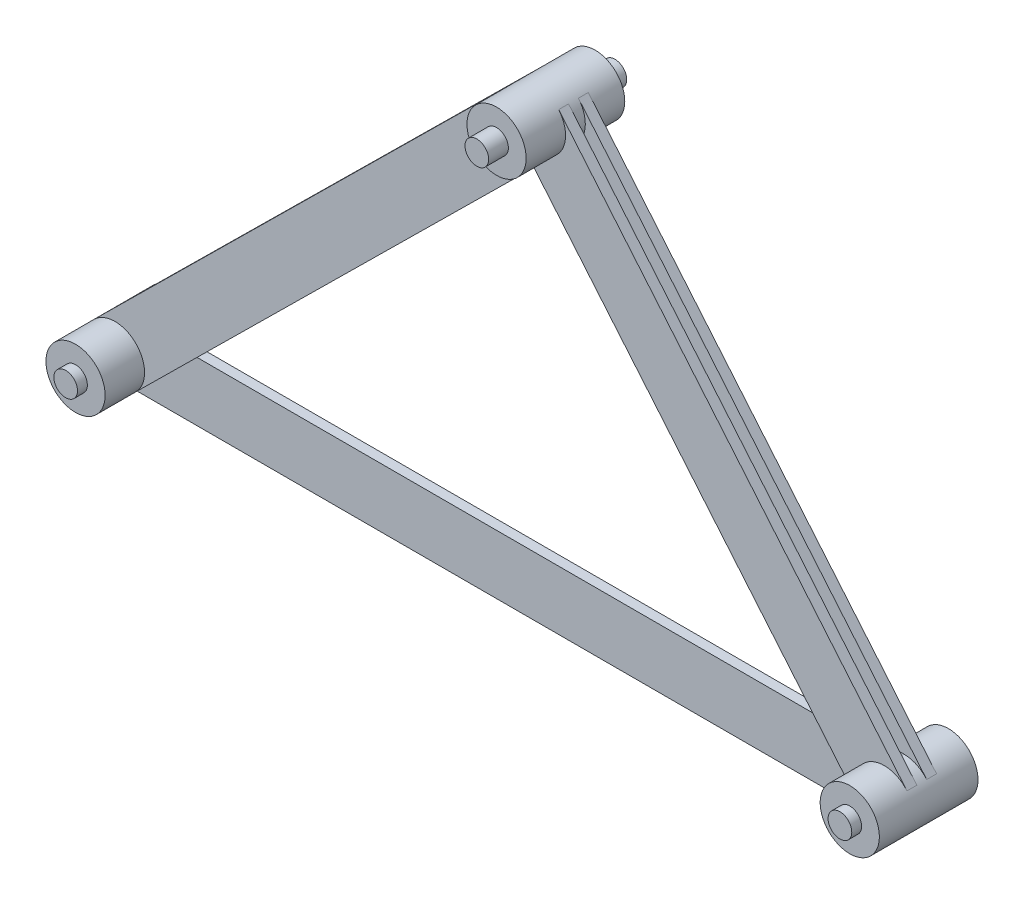
SolidWorks part; units mm, degrees
ref_plane "前视基准面" through (0, 0, 0) normal (0, 0, 1) x (1, 0, 0)
ref_plane "上视基准面" through (0, 0, 0) normal (0, 1, 0) x (1, 0, 0)
ref_plane "右视基准面" through (0, 0, 0) normal (1, 0, 0) x (0, 0, -1)
sketch "草图1" plane through (0, 0, 0) normal (0, 0, 1) x (1, 0, 0)
  line L0 (0, 0) -> (390, 0) construction
  line L1 (0, 15) -> (390, 15)
  line L2 (0, -15) -> (390, -15)
  arc A0 (0, 15) -> (0, -15) centre (0, 0) ccw
  arc A1 (390, -15) -> (390, 15) centre (390, 0) ccw
  point P3 (195, 0)
  dimension "D1" = 390
  dimension "D2" = 30
extrude "凸台-拉伸1" add sketch "草图1" along normal mid plane 5
sketch "草图2" plane through (0, 0, 0) normal (0, 0, 1) x (1, 0, 0)
  line L0 (0, 0) -> (213.4295, 210.8266) construction
  line L1 (390, 0) -> (213.4295, 210.8266) construction
  dimension "D1" = 300
  dimension "D2" = 275
sketch "草图3" plane through (0, 0, 0) normal (0, 0, 1) x (1, 0, 0)
  circle A0 centre (390, 0) radius 15
extrude "凸台-拉伸2" add sketch "草图3" along normal mid plane 50
sketch "草图4" plane through (0, 0, 25) normal (0, 0, 1) x (1, 0, 0)
  circle A0 centre (390, 0) radius 6
  dimension "D1" = 12
extrude "凸台-拉伸3" add sketch "草图4" along normal blind 5
sketch "草图5" plane through (0, 0, 2.5) normal (0, 0, 1) x (1, 0, 0)
  line L0 (213.4295, 210.8266) -> (390, 0) construction
  line L1 (224.9291, 220.4577) -> (401.4996, 9.6311)
  line L2 (201.9299, 201.1955) -> (378.5004, -9.6311)
  arc A0 (224.9291, 220.4577) -> (201.9299, 201.1955) centre (213.4295, 210.8266) ccw
  arc A1 (378.5004, -9.6311) -> (401.4996, 9.6311) centre (390, 0) ccw
  point P4 (301.7147, 105.4133)
  dimension "D1" = 30
extrude "凸台-拉伸4" add sketch "草图5" along normal blind 5
ref_plane "基准面1" through (0, 0, 0) normal (0, 0, -1) x (-1, 0, 0)
sketch "草图6" plane through (0, 0, 2.5) normal (0, 0, 1) x (1, 0, 0)
  line L0 (0, 0) -> (213.4295, 210.8266) construction
  line L1 (-10.5413, 10.6715) -> (202.8882, 221.4981)
  line L2 (10.5413, -10.6715) -> (223.9708, 200.1551)
  arc A0 (-10.5413, 10.6715) -> (10.5413, -10.6715) centre (0, 0) ccw
  arc A1 (223.9708, 200.1551) -> (202.8882, 221.4981) centre (213.4295, 210.8266) ccw
  point P4 (106.7147, 105.4133)
  dimension "D1" = 30
extrude "凸台-拉伸5" add sketch "草图6" along normal blind 5
mirror "镜向1" about plane through (0, 0, 0) normal (0, 0, 1) of "凸台-拉伸5", "凸台-拉伸3", "凸台-拉伸4"
sketch "草图9" plane through (0, 0, 2.5) normal (0, 0, 1) x (1, 0, 0)
  circle A0 centre (0, 0) radius 15
extrude "凸台-拉伸8" add sketch "草图9" along normal mid plane 50
sketch "草图10" plane through (0, 0, 2.5) normal (0, 0, 1) x (1, 0, 0)
  circle A0 centre (0, 0) radius 6
  dimension "D1" = 12
extrude "凸台-拉伸9" add sketch "草图10" along normal mid plane 60
sketch "草图7" plane through (0, 0, 2.5) normal (0, 0, 1) x (1, 0, 0)
  circle A0 centre (213.4295, 210.8266) radius 15
  dimension "D1" = 30
extrude "凸台-拉伸6" add sketch "草图7" along normal mid plane 50
sketch "草图8" plane through (0, 0, 27.5) normal (0, 0, 1) x (1, 0, 0)
  circle A0 centre (213.4295, 210.8266) radius 6
  dimension "D1" = 12
extrude "凸台-拉伸7" add sketch "草图8" along normal blind 10
mirror "镜向2" about plane through (213.4295, 210.8266, 2.5) normal (0, 0, 1) of "凸台-拉伸7"
